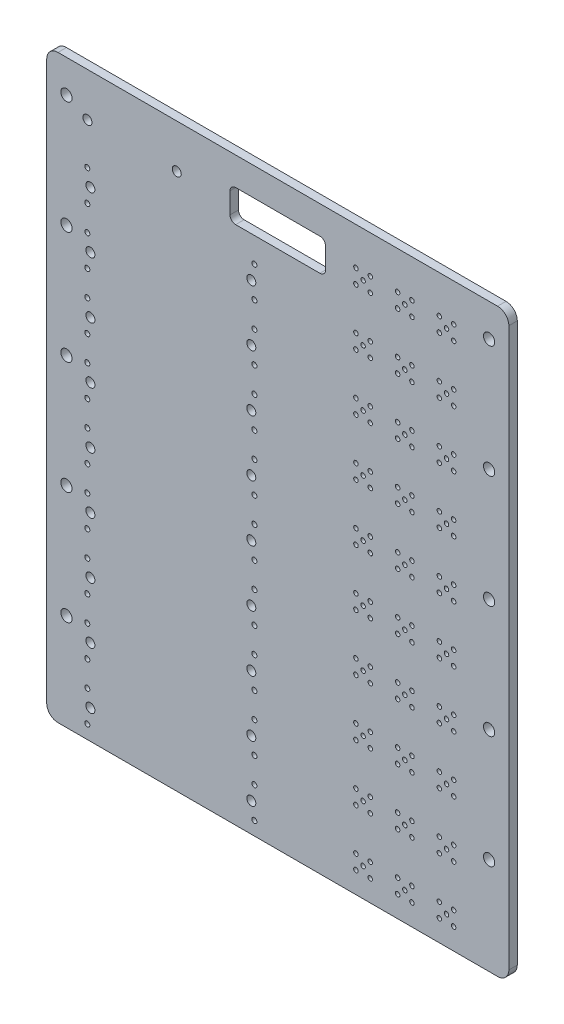
SolidWorks part; units mm, degrees
ref_plane "Front Plane" through (0, 0, 0) normal (0, 0, 1) x (1, 0, 0)
ref_plane "Top Plane" through (0, 0, 0) normal (0, 1, 0) x (1, 0, 0)
ref_plane "Right Plane" through (0, 0, 0) normal (1, 0, 0) x (0, 0, -1)
ref_plane "Plane4" through (0, 0, 0) normal (0, 0, -1) x (-1, 0, 0)
sketch "Sketch1" plane through (0, 0, 0) normal (0, 0, -1) x (-1, 0, 0)
  line L0 (7.475, 96.3) -> (-7.475, 96.3)
  line L1 (-8.475, 97.3) -> (-8.475, 101)
  line L2 (-7.475, 102) -> (7.475, 102)
  line L3 (8.475, 101) -> (8.475, 97.3)
  line L4 (39, 107) -> (-39, 107)
  line L5 (-41, 105) -> (-41, -105)
  line L6 (-39, -107) -> (39, -107)
  line L7 (41, -105) -> (41, 105)
  line L8 (8.475, -101) -> (8.475, -97.3)
  line L9 (-7.475, -102) -> (7.475, -102)
  line L10 (-8.475, -97.3) -> (-8.475, -101)
  line L11 (7.475, -96.3) -> (-7.475, -96.3)
  line L12 (41, -105) -> (41, -107) construction
  line L13 (41, -107) -> (39, -107) construction
  line L14 (41, 0) -> (-41, 0) construction
  line L15 (0, 107) -> (0, -107) construction
  arc A0 (8.475, 97.3) -> (7.475, 96.3) centre (7.475, 97.3) cw
  arc A1 (-7.475, 96.3) -> (-8.475, 97.3) centre (-7.475, 97.3) cw
  arc A2 (-8.475, 101) -> (-7.475, 102) centre (-7.475, 101) cw
  arc A3 (7.475, 102) -> (8.475, 101) centre (7.475, 101) cw
  circle A4 centre (34.325, -40.5) radius 0.45
  circle A5 centre (5.225, -43.25) radius 0.8
  circle A6 centre (-37.5, 21.2) radius 1
  circle A7 centre (5.225, -33.25) radius 0.8
  circle A8 centre (34.325, 46.5) radius 0.45
  circle A9 centre (33.775, -53.25) radius 0.8
  circle A10 centre (34.325, 82) radius 0.45
  circle A11 centre (4.675, 66.5) radius 0.45
  circle A12 centre (33.775, 19.25) radius 0.8
  circle A13 centre (4.675, -0.5) radius 0.45
  circle A14 centre (34.325, 26.5) radius 0.45
  circle A15 centre (5.225, -73.25) radius 0.8
  circle A16 centre (34.325, -66) radius 0.45
  circle A17 centre (5.225, 29.25) radius 0.8
  circle A18 centre (34.325, -80.5) radius 0.45
  circle A19 centre (34.325, 36.5) radius 0.45
  circle A20 centre (4.675, 22) radius 0.45
  circle A21 centre (33.775, -23.25) radius 0.8
  circle A22 centre (5.225, 19.25) radius 0.8
  circle A23 centre (33.775, -13.25) radius 0.8
  circle A24 centre (4.675, -10.5) radius 0.45
  circle A25 centre (34.325, 52) radius 0.45
  circle A26 centre (5.225, 89.25) radius 0.8
  circle A27 centre (5.225, -53.25) radius 0.8
  circle A28 centre (34.325, -70.5) radius 0.45
  circle A29 centre (34.325, -36) radius 0.45
  circle A30 centre (5.225, 59.25) radius 0.8
  circle A31 centre (33.775, 59.25) radius 0.8
  circle A32 centre (34.325, 32) radius 0.45
  circle A33 centre (33.775, -73.25) radius 0.8
  circle A34 centre (4.675, 46.5) radius 0.45
  circle A35 centre (4.675, 26.5) radius 0.45
  circle A36 centre (34.325, -6) radius 0.45
  circle A37 centre (34.325, -20.5) radius 0.45
  circle A38 centre (34.325, -60.5) radius 0.45
  circle A39 centre (5.225, -83.25) radius 0.8
  circle A40 centre (5.225, -13.25) radius 0.8
  circle A41 centre (33.775, -83.25) radius 0.8
  circle A42 centre (34.325, 92) radius 0.45
  circle A43 centre (33.775, -93.25) radius 0.8
  circle A44 centre (4.675, 32) radius 0.45
  circle A45 centre (4.675, 16.5) radius 0.45
  circle A46 centre (34.325, -50.5) radius 0.45
  circle A47 centre (4.675, 76.5) radius 0.45
  circle A48 centre (4.675, 82) radius 0.45
  circle A49 centre (34.325, 16.5) radius 0.45
  circle A50 centre (34.325, -56) radius 0.45
  circle A51 centre (5.225, -3.25) radius 0.8
  circle A52 centre (4.675, 36.5) radius 0.45
  circle A53 centre (4.675, -36) radius 0.45
  circle A54 centre (34.325, 86.5) radius 0.45
  circle A55 centre (33.775, 29.25) radius 0.8
  circle A56 centre (4.675, -26) radius 0.45
  circle A57 centre (4.675, -56) radius 0.45
  circle A58 centre (34.325, -30.5) radius 0.45
  circle A59 centre (33.775, 39.25) radius 0.8
  circle A60 centre (4.675, 56.5) radius 0.45
  circle A61 centre (34.325, 12) radius 0.45
  arc A62 (-39, 107) -> (-41, 105) centre (-39, 105) ccw
  arc A63 (-41, -105) -> (-39, -107) centre (-39, -105) ccw
  arc A64 (39, -107) -> (41, -105) centre (39, -105) ccw
  arc A65 (41, 105) -> (39, 107) centre (39, 105) ccw
  circle A66 centre (5.225, -63.25) radius 0.8
  circle A67 centre (4.675, -6) radius 0.45
  circle A68 centre (5.225, 49.25) radius 0.8
  circle A69 centre (4.675, -16) radius 0.45
  circle A70 centre (33.775, 9.25) radius 0.8
  circle A71 centre (4.675, -76) radius 0.45
  circle A72 centre (34.325, -76) radius 0.45
  circle A73 centre (4.675, -66) radius 0.45
  circle A74 centre (4.675, -30.5) radius 0.45
  circle A75 centre (34.325, 72) radius 0.45
  circle A76 centre (33.775, -63.25) radius 0.8
  circle A77 centre (33.775, 99.25) radius 0.8
  circle A78 centre (4.675, -86) radius 0.45
  circle A79 centre (4.675, 62) radius 0.45
  circle A80 centre (-37.5, 101.2) radius 1
  circle A81 centre (34.325, 76.5) radius 0.45
  circle A82 centre (4.675, -80.5) radius 0.45
  circle A83 centre (33.775, 49.25) radius 0.8
  circle A84 centre (4.675, 86.5) radius 0.45
  circle A85 centre (33.775, -33.25) radius 0.8
  circle A86 centre (4.675, 6.5) radius 0.45
  circle A87 centre (33.775, 79.25) radius 0.8
  circle A88 centre (34.325, -26) radius 0.45
  circle A89 centre (4.675, -60.5) radius 0.45
  circle A90 centre (4.675, 42) radius 0.45
  circle A91 centre (5.225, -23.25) radius 0.8
  circle A92 centre (34.325, 66.5) radius 0.45
  circle A93 centre (5.225, 79.25) radius 0.8
  circle A94 centre (4.675, -20.5) radius 0.45
  circle A95 centre (33.775, 89.25) radius 0.8
  circle A96 centre (17.925, -93.25) radius 0.8
  circle A97 centre (34.325, 22) radius 0.45
  circle A98 centre (4.675, 72) radius 0.45
  circle A99 centre (17.925, 99.25) radius 0.8
  circle A100 centre (4.675, 12) radius 0.45
  circle A101 centre (33.775, -3.25) radius 0.8
  circle A102 centre (34.325, 56.5) radius 0.45
  circle A103 centre (4.675, -70.5) radius 0.45
  circle A104 centre (34.325, -16) radius 0.45
  circle A105 centre (5.225, 39.25) radius 0.8
  circle A106 centre (34.325, -10.5) radius 0.45
  circle A107 centre (4.675, -50.5) radius 0.45
  circle A108 centre (-21.27, -2.0788) radius 0.4
  circle A109 centre (-31.21, -42.0789) radius 0.4
  circle A110 centre (-23.81, -44.6189) radius 0.4
  circle A111 centre (-15.14, -23.3489) radius 0.4
  circle A112 centre (-31.21, -44.6189) radius 0.4
  circle A114 centre (-16.41, -12.0788) radius 0.4
  circle A115 centre (-13.87, -24.6188) radius 0.4
  circle A116 centre (-21.27, -44.6189) radius 0.4
  circle A117 centre (-31.21, -4.6188) radius 0.4
  circle A118 centre (-15.14, -13.3489) radius 0.4
  circle A119 centre (-22.54, -13.3489) radius 0.4
  circle A120 centre (-31.21, -14.6189) radius 0.4
  circle A121 centre (-23.81, -22.0788) radius 0.4
  circle A122 centre (-29.94, -13.3489) radius 0.4
  circle A123 centre (-13.87, -12.0788) radius 0.4
  circle A124 centre (-28.67, -12.0788) radius 0.4
  circle A125 centre (-29.94, -43.3488) radius 0.4
  circle A126 centre (-22.54, -43.3488) radius 0.4
  circle A127 centre (-31.21, -2.0788) radius 0.4
  circle A128 centre (-23.81, -14.6189) radius 0.4
  circle A129 centre (-23.81, -12.0788) radius 0.4
  circle A130 centre (-16.41, -22.0788) radius 0.4
  circle A131 centre (-29.94, -3.3488) radius 0.4
  circle A132 centre (-21.27, -42.0789) radius 0.4
  circle A133 centre (-13.87, -14.6189) radius 0.4
  circle A134 centre (-15.14, -43.3488) radius 0.4
  circle A135 centre (-13.87, -42.0789) radius 0.4
  circle A136 centre (-16.41, -44.6189) radius 0.4
  circle A137 centre (-21.27, -24.6188) radius 0.4
  circle A138 centre (-23.81, -24.6188) radius 0.4
  circle A139 centre (-28.67, -4.6188) radius 0.4
  circle A140 centre (-16.41, -24.6188) radius 0.4
  circle A141 centre (-28.67, -44.6189) radius 0.4
  circle A142 centre (-21.27, -12.0788) radius 0.4
  circle A143 centre (-28.67, -42.0789) radius 0.4
  circle A144 centre (-13.87, -44.6189) radius 0.4
  circle A145 centre (-23.81, -42.0789) radius 0.4
  circle A146 centre (-28.67, -14.6189) radius 0.4
  circle A147 centre (-16.41, -42.0789) radius 0.4
  circle A148 centre (-31.21, -12.0788) radius 0.4
  circle A149 centre (-21.27, -14.6189) radius 0.4
  circle A150 centre (-13.87, -22.0788) radius 0.4
  circle A151 centre (-16.41, -14.6189) radius 0.4
  circle A152 centre (-22.54, -23.3489) radius 0.4
  circle A153 centre (-23.81, -2.0788) radius 0.4
  circle A154 centre (-23.81, -4.6188) radius 0.4
  circle A155 centre (-22.54, -3.3488) radius 0.4
  circle A156 centre (-21.27, -4.6188) radius 0.4
  circle A157 centre (-13.87, -2.0788) radius 0.4
  circle A158 centre (-16.41, -2.0788) radius 0.4
  circle A159 centre (-16.41, -4.6188) radius 0.4
  circle A160 centre (-15.14, -3.3488) radius 0.4
  circle A161 centre (-13.87, -4.6188) radius 0.4
  circle A162 centre (-28.67, -2.0788) radius 0.4
  circle A163 centre (-28.67, 10.4212) radius 0.4
  circle A164 centre (-31.21, 10.4212) radius 0.4
  circle A165 centre (-31.21, 7.8812) radius 0.4
  circle A166 centre (-29.94, 9.1512) radius 0.4
  circle A167 centre (-28.67, 7.8812) radius 0.4
  circle A168 centre (-21.27, 10.4212) radius 0.4
  circle A169 centre (-23.81, 10.4212) radius 0.4
  circle A170 centre (-23.81, 7.8812) radius 0.4
  circle A171 centre (-22.54, 9.1512) radius 0.4
  circle A172 centre (-21.27, 7.8812) radius 0.4
  circle A173 centre (-13.87, -54.6189) radius 0.4
  circle A174 centre (-15.14, -53.3489) radius 0.4
  circle A175 centre (-16.41, -54.6189) radius 0.4
  circle A176 centre (-16.41, -52.0789) radius 0.4
  circle A177 centre (-13.87, -52.0789) radius 0.4
  circle A178 centre (-21.27, -54.6189) radius 0.4
  circle A179 centre (-22.54, -53.3489) radius 0.4
  circle A180 centre (-23.81, -54.6189) radius 0.4
  circle A181 centre (-23.81, -52.0789) radius 0.4
  circle A182 centre (-21.27, -52.0789) radius 0.4
  circle A183 centre (-28.67, -54.6189) radius 0.4
  circle A184 centre (-29.94, -53.3489) radius 0.4
  circle A185 centre (-31.21, -54.6189) radius 0.4
  circle A186 centre (-31.21, -52.0789) radius 0.4
  circle A187 centre (-28.67, -52.0789) radius 0.4
  circle A188 centre (-13.87, 10.4212) radius 0.4
  circle A189 centre (-16.41, 10.4212) radius 0.4
  circle A190 centre (-16.41, 7.8812) radius 0.4
  circle A191 centre (-15.14, 9.1512) radius 0.4
  circle A192 centre (-13.87, 7.8812) radius 0.4
  circle A193 centre (-28.67, 20.4212) radius 0.4
  circle A194 centre (-31.21, 20.4212) radius 0.4
  circle A195 centre (-31.21, 17.8812) radius 0.4
  circle A196 centre (-29.94, 19.1512) radius 0.4
  circle A197 centre (-28.67, 17.8812) radius 0.4
  circle A198 centre (-21.27, 20.4212) radius 0.4
  circle A199 centre (-23.81, 20.4212) radius 0.4
  circle A200 centre (-23.81, 17.8812) radius 0.4
  circle A201 centre (-22.54, 19.1512) radius 0.4
  circle A202 centre (-21.27, 17.8812) radius 0.4
  circle A203 centre (-13.87, 20.4212) radius 0.4
  circle A204 centre (-16.41, 20.4212) radius 0.4
  circle A205 centre (-16.41, 17.8812) radius 0.4
  circle A206 centre (-15.14, 19.1512) radius 0.4
  circle A207 centre (-13.87, 17.8812) radius 0.4
  circle A208 centre (-28.67, 30.4212) radius 0.4
  circle A209 centre (-31.21, 30.4212) radius 0.4
  circle A210 centre (-31.21, 27.8812) radius 0.4
  circle A211 centre (-29.94, 29.1512) radius 0.4
  circle A212 centre (-28.67, 27.8812) radius 0.4
  circle A213 centre (-21.27, 30.4212) radius 0.4
  circle A214 centre (-23.81, 30.4212) radius 0.4
  circle A215 centre (-23.81, 27.8812) radius 0.4
  circle A216 centre (-22.54, 29.1512) radius 0.4
  circle A217 centre (-21.27, 27.8812) radius 0.4
  circle A218 centre (-13.87, 30.4212) radius 0.4
  circle A219 centre (-16.41, 30.4212) radius 0.4
  circle A220 centre (-16.41, 27.8812) radius 0.4
  circle A221 centre (-15.14, 29.1512) radius 0.4
  circle A222 centre (-13.87, 27.8812) radius 0.4
  circle A223 centre (-28.67, 40.4211) radius 0.4
  circle A224 centre (-31.21, 40.4211) radius 0.4
  circle A225 centre (-31.21, 37.8812) radius 0.4
  circle A226 centre (-29.94, 39.1512) radius 0.4
  circle A227 centre (-28.67, 37.8812) radius 0.4
  circle A228 centre (-13.87, -64.6188) radius 0.4
  circle A229 centre (-15.14, -63.3488) radius 0.4
  circle A230 centre (-16.41, -64.6188) radius 0.4
  circle A231 centre (-16.41, -62.0789) radius 0.4
  circle A232 centre (-13.87, -62.0789) radius 0.4
  circle A233 centre (-21.27, -64.6188) radius 0.4
  circle A234 centre (-22.54, -63.3488) radius 0.4
  circle A235 centre (-23.81, -64.6188) radius 0.4
  circle A236 centre (-23.81, -62.0789) radius 0.4
  circle A237 centre (-21.27, -62.0789) radius 0.4
  circle A238 centre (-28.67, -64.6188) radius 0.4
  circle A239 centre (-29.94, -63.3488) radius 0.4
  circle A240 centre (-31.21, -64.6188) radius 0.4
  circle A241 centre (-31.21, -62.0789) radius 0.4
  circle A242 centre (-28.67, -62.0789) radius 0.4
  circle A243 centre (-21.27, 40.4211) radius 0.4
  circle A244 centre (-23.81, 40.4211) radius 0.4
  circle A245 centre (-23.81, 37.8812) radius 0.4
  circle A246 centre (-22.54, 39.1512) radius 0.4
  circle A247 centre (-21.27, 37.8812) radius 0.4
  circle A248 centre (-13.87, 40.4211) radius 0.4
  circle A249 centre (-16.41, 40.4211) radius 0.4
  circle A250 centre (-16.41, 37.8812) radius 0.4
  circle A251 centre (-15.14, 39.1512) radius 0.4
  circle A252 centre (-13.87, 37.8812) radius 0.4
  circle A253 centre (-28.67, 50.4211) radius 0.4
  circle A254 centre (-31.21, 50.4211) radius 0.4
  circle A255 centre (-31.21, 47.8811) radius 0.4
  circle A256 centre (-29.94, 49.1512) radius 0.4
  circle A257 centre (-28.67, 47.8811) radius 0.4
  circle A258 centre (-21.27, 50.4211) radius 0.4
  circle A259 centre (-23.81, 50.4211) radius 0.4
  circle A260 centre (-23.81, 47.8811) radius 0.4
  circle A261 centre (-22.54, 49.1512) radius 0.4
  circle A262 centre (-21.27, 47.8811) radius 0.4
  circle A263 centre (-13.87, 50.4211) radius 0.4
  circle A264 centre (-16.41, 50.4211) radius 0.4
  circle A265 centre (-16.41, 47.8811) radius 0.4
  circle A266 centre (-15.14, 49.1512) radius 0.4
  circle A267 centre (-13.87, 47.8811) radius 0.4
  circle A268 centre (-28.67, 60.4211) radius 0.4
  circle A269 centre (-31.21, 60.4211) radius 0.4
  circle A270 centre (-31.21, 57.8811) radius 0.4
  circle A271 centre (-29.94, 59.1512) radius 0.4
  circle A272 centre (-28.67, 57.8811) radius 0.4
  circle A273 centre (-21.27, 60.4211) radius 0.4
  circle A274 centre (-23.81, 60.4211) radius 0.4
  circle A275 centre (-23.81, 57.8811) radius 0.4
  circle A276 centre (-22.54, 59.1512) radius 0.4
  circle A277 centre (-21.27, 57.8811) radius 0.4
  circle A278 centre (-13.87, 60.4211) radius 0.4
  circle A279 centre (-16.41, 60.4211) radius 0.4
  circle A280 centre (-16.41, 57.8811) radius 0.4
  circle A281 centre (-15.14, 59.1512) radius 0.4
  circle A282 centre (-13.87, 57.8811) radius 0.4
  circle A283 centre (-13.87, -74.6188) radius 0.4
  circle A284 centre (-15.14, -73.3489) radius 0.4
  circle A285 centre (-16.41, -74.6188) radius 0.4
  circle A286 centre (-16.41, -72.0789) radius 0.4
  circle A287 centre (-13.87, -72.0789) radius 0.4
  circle A288 centre (-21.27, -74.6188) radius 0.4
  circle A289 centre (-22.54, -73.3489) radius 0.4
  circle A290 centre (-23.81, -74.6188) radius 0.4
  circle A291 centre (-23.81, -72.0789) radius 0.4
  circle A292 centre (-21.27, -72.0789) radius 0.4
  circle A293 centre (-28.67, -74.6188) radius 0.4
  circle A294 centre (-29.94, -73.3489) radius 0.4
  circle A295 centre (-31.21, -74.6188) radius 0.4
  circle A296 centre (-31.21, -72.0789) radius 0.4
  circle A297 centre (-28.67, -72.0789) radius 0.4
  circle A298 centre (-28.67, 70.4211) radius 0.4
  circle A299 centre (-31.21, 70.4211) radius 0.4
  circle A300 centre (-31.21, 67.8812) radius 0.4
  circle A301 centre (-29.94, 69.1512) radius 0.4
  circle A302 centre (-28.67, 67.8812) radius 0.4
  circle A303 centre (-21.27, 70.4211) radius 0.4
  circle A304 centre (-23.81, 70.4211) radius 0.4
  circle A305 centre (-23.81, 67.8812) radius 0.4
  circle A306 centre (-22.54, 69.1512) radius 0.4
  circle A307 centre (-21.27, 67.8812) radius 0.4
  circle A308 centre (-13.87, 70.4211) radius 0.4
  circle A309 centre (-16.41, 70.4211) radius 0.4
  circle A310 centre (-16.41, 67.8812) radius 0.4
  circle A311 centre (-15.14, 69.1512) radius 0.4
  circle A312 centre (-13.87, 67.8812) radius 0.4
  circle A313 centre (-28.67, 80.4211) radius 0.4
  circle A314 centre (-31.21, 80.4211) radius 0.4
  circle A315 centre (-31.21, 77.8812) radius 0.4
  circle A316 centre (-29.94, 79.1512) radius 0.4
  circle A317 centre (-28.67, 77.8812) radius 0.4
  circle A318 centre (-21.27, 80.4211) radius 0.4
  circle A319 centre (-23.81, 80.4211) radius 0.4
  circle A320 centre (-23.81, 77.8812) radius 0.4
  circle A321 centre (-22.54, 79.1512) radius 0.4
  circle A322 centre (-21.27, 77.8812) radius 0.4
  circle A323 centre (-13.87, 80.4211) radius 0.4
  circle A324 centre (-16.41, 80.4211) radius 0.4
  circle A325 centre (-16.41, 77.8812) radius 0.4
  circle A326 centre (-15.14, 79.1512) radius 0.4
  circle A327 centre (-13.87, 77.8812) radius 0.4
  circle A328 centre (-28.67, 90.4212) radius 0.4
  circle A329 centre (-31.21, 90.4212) radius 0.4
  circle A330 centre (-31.21, 87.8812) radius 0.4
  circle A331 centre (-29.94, 89.1512) radius 0.4
  circle A332 centre (-28.67, 87.8812) radius 0.4
  circle A333 centre (-21.27, 90.4212) radius 0.4
  circle A334 centre (-23.81, 90.4212) radius 0.4
  circle A335 centre (-23.81, 87.8812) radius 0.4
  circle A336 centre (-22.54, 89.1512) radius 0.4
  circle A337 centre (-21.27, 87.8812) radius 0.4
  circle A338 centre (-13.87, -84.6188) radius 0.4
  circle A339 centre (-15.14, -83.3488) radius 0.4
  circle A340 centre (-16.41, -84.6188) radius 0.4
  circle A341 centre (-16.41, -82.0789) radius 0.4
  circle A342 centre (-13.87, -82.0789) radius 0.4
  circle A343 centre (-21.27, -84.6188) radius 0.4
  circle A344 centre (-22.54, -83.3488) radius 0.4
  circle A345 centre (-23.81, -84.6188) radius 0.4
  circle A346 centre (-23.81, -82.0789) radius 0.4
  circle A347 centre (-21.27, -82.0789) radius 0.4
  circle A348 centre (-28.67, -84.6188) radius 0.4
  circle A349 centre (-29.94, -83.3488) radius 0.4
  circle A350 centre (-31.21, -84.6188) radius 0.4
  circle A351 centre (-31.21, -82.0789) radius 0.4
  circle A352 centre (-28.67, -82.0789) radius 0.4
  circle A353 centre (-13.87, 90.4212) radius 0.4
  circle A354 centre (-16.41, 90.4212) radius 0.4
  circle A355 centre (-16.41, 87.8812) radius 0.4
  circle A356 centre (-15.14, 89.1512) radius 0.4
  circle A357 centre (-13.87, 87.8812) radius 0.4
  circle A358 centre (4.675, -40.5) radius 0.45
  circle A359 centre (34.325, -46) radius 0.45
  circle A360 centre (34.325, 6.5) radius 0.45
  circle A361 centre (4.675, 92) radius 0.45
  circle A362 centre (34.325, 62) radius 0.45
  circle A363 centre (34.325, -86) radius 0.45
  circle A364 centre (4.675, -46) radius 0.45
  circle A365 centre (34.325, 42) radius 0.45
  circle A366 centre (5.225, 69.25) radius 0.8
  circle A367 centre (33.775, 69.25) radius 0.8
  circle A368 centre (33.775, -43.25) radius 0.8
  circle A369 centre (5.225, 9.25) radius 0.8
  circle A370 centre (4.675, 52) radius 0.45
  circle A371 centre (34.325, -0.5) radius 0.45
  circle A372 centre (-13.87, -92.0789) radius 0.4
  circle A373 centre (-31.21, -94.6188) radius 0.4
  circle A374 centre (-28.67, -92.0789) radius 0.4
  circle A375 centre (-28.67, -94.6188) radius 0.4
  circle A376 centre (-29.94, -93.3488) radius 0.4
  circle A377 centre (-23.81, -92.0789) radius 0.4
  circle A378 centre (-16.41, -94.6188) radius 0.4
  circle A379 centre (-21.27, -94.6188) radius 0.4
  circle A380 centre (-21.27, -92.0789) radius 0.4
  circle A381 centre (-23.81, -94.6188) radius 0.4
  circle A382 centre (-16.41, -92.0789) radius 0.4
  circle A383 centre (-31.21, -92.0789) radius 0.4
  circle A384 centre (-22.54, -93.3488) radius 0.4
  circle A385 centre (-13.87, -94.6188) radius 0.4
  circle A386 centre (-15.14, -93.3488) radius 0.4
  circle A387 centre (-21.27, -22.0788) radius 0.4
  circle A388 centre (-28.67, -24.6188) radius 0.4
  circle A389 centre (-29.94, -23.3489) radius 0.4
  circle A390 centre (-31.21, -24.6188) radius 0.4
  circle A391 centre (-31.21, -22.0788) radius 0.4
  circle A392 centre (-28.67, -22.0788) radius 0.4
  circle A393 centre (-13.87, -34.6189) radius 0.4
  circle A394 centre (-15.14, -33.3488) radius 0.4
  circle A395 centre (-16.41, -34.6189) radius 0.4
  circle A396 centre (-16.41, -32.0789) radius 0.4
  circle A397 centre (-13.87, -32.0789) radius 0.4
  circle A398 centre (-21.27, -34.6189) radius 0.4
  circle A399 centre (-22.54, -33.3488) radius 0.4
  circle A400 centre (-23.81, -34.6189) radius 0.4
  circle A401 centre (-23.81, -32.0789) radius 0.4
  circle A402 centre (-21.27, -32.0789) radius 0.4
  circle A403 centre (-28.67, -34.6189) radius 0.4
  circle A404 centre (-29.94, -33.3488) radius 0.4
  circle A405 centre (-31.21, -34.6189) radius 0.4
  circle A406 centre (-31.21, -32.0789) radius 0.4
  circle A407 centre (-28.67, -32.0789) radius 0.4
  circle A408 centre (-37.5, -81.2) radius 1
  circle A409 centre (37.5, 81.2) radius 1
  circle A412 centre (-37.5, 41.2) radius 1
  circle A413 centre (-37.5, -41.2) radius 1
  circle A414 centre (-37.5, -101.2) radius 1
  circle A415 centre (-37.5, 61.2) radius 1
  circle A416 centre (37.5, 61.2) radius 1
  circle A417 centre (-37.5, 81.2) radius 1
  circle A420 centre (-37.5, -61.2) radius 1
  circle A421 centre (37.5, 41.2) radius 1
  circle A422 centre (-37.5, -21.2) radius 1
  circle A423 centre (37.5, 101.2) radius 1
  circle A424 centre (37.5, 21.2) radius 1
  arc A425 (8.475, -97.3) -> (7.475, -96.3) centre (7.475, -97.3) ccw
  arc A426 (7.475, -102) -> (8.475, -101) centre (7.475, -101) ccw
  arc A427 (-8.475, -101) -> (-7.475, -102) centre (-7.475, -101) ccw
  arc A428 (-7.475, -96.3) -> (-8.475, -97.3) centre (-7.475, -97.3) ccw
  point P876 (0, 102)
  dimension "D3" = 2
  dimension "D4" = 1
  dimension "D9" = 2
  dimension "D1" = 82
  dimension "D2" = 214
  dimension "D5" = 16.95
  dimension "D6" = 5.7
  dimension "D7" = 5
  dimension "D8" = 5
  dimension "D10" = 5.8
  dimension "D11" = 3.5
  dimension "D12" = 20
extrude "Boss-Extrude1" [suppressed] add sketch "Sketch1" against normal blind 1.5
sketch "Sketch2" plane through (0, 0, 0) normal (0, 0, 1) x (1, 0, 0)
  line L0 (82, 103) -> (0, 103)
  line L1 (0, 103) -> (0, 0)
  line L2 (0, 0) -> (82, 0)
  line L3 (82, 0) -> (82, 103)
  dimension "D1" = 82
  dimension "D2" = 103
extrude "mainBoard" add sketch "Sketch2" along normal blind 1.5
ref_plane "X_mirror" through (41, 0, 0) normal (-1, 0, 0) x (0, 0, 1)
sketch "Sketch3" plane through (0, 0, 1.5) normal (0, 0, 1) x (1, 0, 0)
  line L0 (82, 103) -> (0, 103) construction
  line L1 (41, 103) -> (41, 0) construction
  line L2 (0, 0) -> (82, 0) construction
  line L5 (32.525, 98) -> (49.475, 98)
  line L6 (32.525, 98) -> (32.525, 92.3)
  line L7 (32.525, 92.3) -> (49.475, 92.3)
  line L8 (49.475, 98) -> (49.475, 92.3)
  point P6 (41, 98)
  dimension "D1" = 5
  dimension "D3" = 16.95
  dimension "D4" = 5.7
extrude "solarHole" cut sketch "Sketch3" against normal through all
fillet "Fillet1" radius 2 4 edges at (0, 0, 0.75) (82, 0, 0.75) (82, 103, 0.75) (0, 103, 0.75)
fillet "Fillet2" radius 1 4 edges at (49.475, 92.3, 0.75) (49.475, 98, 0.75) (32.525, 92.3, 0.75) (32.525, 98, 0.75)
hole_wizard "Ø2.0mm Hole_screw" positions "Sketch4" profile "Sketch5" hole size "Ø2.0" standard "ANSI Metric"
sketch "Sketch4" plane through (0, 0, 1.5) normal (0, 0, 1) x (1, 0, 0)
  line L0 (80, 103) -> (2, 103) construction
  line L1 (0, 101) -> (0, 2) construction
  point P0 (3.5, 97.2)
  dimension "D1" = 5.8
  dimension "D2" = 3.5
sketch "Sketch5" plane through (3.5, 97.2, 1.5) normal (1, 0, 0) x (0, -1, 0)
  line L0 (0, 0) -> (0, 10.1259)
  line L1 (0, 10.1259) -> (1, 9.525)
  line L2 (1, 9.525) -> (1, 0)
  line L5 (1, 0) -> (0, 0)
  line L10 (0, 10.1259) -> (-1, 9.525) construction
  line L11 (0, -6.35) -> (0, 107.95) construction
  dimension "Hole Dia." = 2
  dimension "Hole Depth" = 9.525
  dimension "Drill Angle" = 118
hole_wizard "Ø1.6mm Hole_20pin" positions "Sketch12" profile "Sketch13" hole size "Ø1.5" standard "ANSI Metric"
sketch "Sketch12" plane through (0, 0, 1.5) normal (0, 0, 1) x (1, 0, 0)
  line L0 (80, 103) -> (2, 103) construction
  line L1 (0, 101) -> (0, 2) construction
  point P0 (7.225, 95.25)
  point P2 (23.075, 95.25)
  dimension "D1" = 15.85
  dimension "D2" = 7.75
  dimension "D3" = 7.225
sketch "Sketch13" plane through (7.225, 95.25, 1.5) normal (1, 0, 0) x (0, -1, 0)
  line L0 (0, 0) -> (0, 10.0057)
  line L1 (0, 10.0057) -> (0.8, 9.525)
  line L2 (0.8, 9.525) -> (0.8, 0)
  line L5 (0.8, 0) -> (0, 0)
  line L10 (0, 10.0057) -> (-0.8, 9.525) construction
  line L11 (0, -6.35) -> (0, 107.95) construction
  dimension "Hole Dia." = 1.6
  dimension "Hole Depth" = 9.525
  dimension "Drill Angle" = 118
hole_wizard "Ø1.6mm Hole_40pn_big" positions "Sketch6" profile "Sketch7" hole size "Ø1.5" standard "ANSI Metric"
sketch "Sketch6" plane through (0, 0, 1.5) normal (0, 0, 1) x (1, 0, 0)
  line L0 (0, 101) -> (0, 2) construction
  line L1 (80, 103) -> (2, 103) construction
  point P14 (7.75, 85.15)
  point P16 (36.3, 85.15)
  dimension "D1" = 7.75
  dimension "D7" = 17.85
  dimension "D8" = 28.55
sketch "Sketch7" plane through (7.75, 85.15, 1.5) normal (1, 0, 0) x (0, -1, 0)
  line L0 (0, 0) -> (0, 10.0057)
  line L1 (0, 10.0057) -> (0.8, 9.525)
  line L2 (0.8, 9.525) -> (0.8, 0)
  line L5 (0.8, 0) -> (0, 0)
  line L10 (0, 10.0057) -> (-0.8, 9.525) construction
  line L11 (0, -6.35) -> (0, 107.95) construction
  dimension "Hole Dia." = 1.6
  dimension "Hole Depth" = 9.525
  dimension "Drill Angle" = 118
hole_wizard "Ø0.8mm MMCX Hole" positions "Sketch8" profile "Sketch9" hole size "Ø1.0" standard "ANSI Metric"
sketch "Sketch8" plane through (0, 0, 1.5) normal (0, 0, 1) x (1, 0, 0)
  line L0 (69.67, 86.32) -> (72.21, 83.78) construction
  line L2 (80, 103) -> (2, 103) construction
  line L3 (82, 2) -> (82, 101) construction
  point P0 (70.94, 85.05)
  point P2 (69.67, 86.32)
  point P4 (72.21, 86.32)
  point P6 (72.21, 83.78)
  point P8 (69.67, 83.78)
  point P21 (70.94, 85.05)
  dimension "D1" = 2.54
  dimension "D2" = 2.54
  dimension "D3" = 17.95
  dimension "D4" = 11.06
sketch "Sketch9" plane through (70.94, 85.05, 1.5) normal (1, 0, 0) x (0, -1, 0)
  line L0 (0, 0) -> (0, 9.7653)
  line L1 (0, 9.7653) -> (0.4, 9.525)
  line L2 (0.4, 9.525) -> (0.4, 0)
  line L5 (0.4, 0) -> (0, 0)
  line L10 (0, 9.7653) -> (-0.4, 9.525) construction
  line L11 (0, -6.35) -> (0, 107.95) construction
  dimension "Hole Dia." = 0.8
  dimension "Hole Depth" = 9.525
  dimension "Drill Angle" = 118
hole_wizard "Ø0.9mm Hole_40pin_tiny" positions "Sketch10" profile "Sketch11" hole size "Ø1.5" standard "ANSI Metric"
sketch "Sketch10" plane through (0, 0, 1.5) normal (0, 0, 1) x (1, 0, 0)
  line L1 (7.75, 85.15) -> (36.3, 85.15) construction
  line L3 (22.025, -11.0236) -> (22.025, 181.3236) construction
  circle A0 centre (7.75, 85.15) radius 0.8 construction
  point P0 (7.2, 87.9)
  point P24 (22.025, 85.15)
  point P25 (22.025, 85.15)
  point P27 (7.2, 82.4)
  point P29 (36.85, 87.9)
  point P30 (36.85, 82.4)
  dimension "D1" = 0.55
  dimension "D2" = 5.5
sketch "Sketch11" plane through (7.2, 87.9, 1.5) normal (1, 0, 0) x (0, -1, 0)
  line L0 (0, 0) -> (0, 9.7954)
  line L1 (0, 9.7954) -> (0.45, 9.525)
  line L2 (0.45, 9.525) -> (0.45, 0)
  line L5 (0.45, 0) -> (0, 0)
  line L10 (0, 9.7954) -> (-0.45, 9.525) construction
  line L11 (0, -6.35) -> (0, 107.95) construction
  dimension "Hole Dia." = 0.9
  dimension "Hole Depth" = 9.525
  dimension "Drill Angle" = 118
pattern_linear "MMCX_intra-card" count 3 spacing 7.4 along (-1, 0, 0) of "Ø0.8mm MMCX Hole"
pattern_linear "Zpos_block" count 9 spacing 10 along (0, -1, 0) of "MMCX_intra-card", "Ø0.9mm Hole_40pin_tiny", "Ø1.6mm Hole_40pn_big"
pattern_linear "Zpos_antennaMMCX" count 2 spacing 10 along (0, 1, 0) of "MMCX_intra-card"
pattern_linear "screwHoles_intra-rail" count 5 spacing 20 along (0, -1, 0) of "Ø2.0mm Hole_screw"
pattern_linear "Zneg_block" [suppressed] count 2 spacing 92.4 of bodies 107
pattern_linear "Zneg_antennaMMCX" [suppressed] count 3 spacing 10 of bodies 107
ref_plane "Y_mirror" through (0, 51.5, 0) normal (0, 1, 0) x (1, 0, 0)
mirror "screwHoles_trans-rail" about plane through (41, 0, 0) normal (-1, 0, 0) of "Ø2.0mm Hole_screw", "screwHoles_intra-rail"
mirror "screwHoles_Zneg_block" [suppressed] about plane through (0, 51.5, 0) normal (0, 1, 0)
